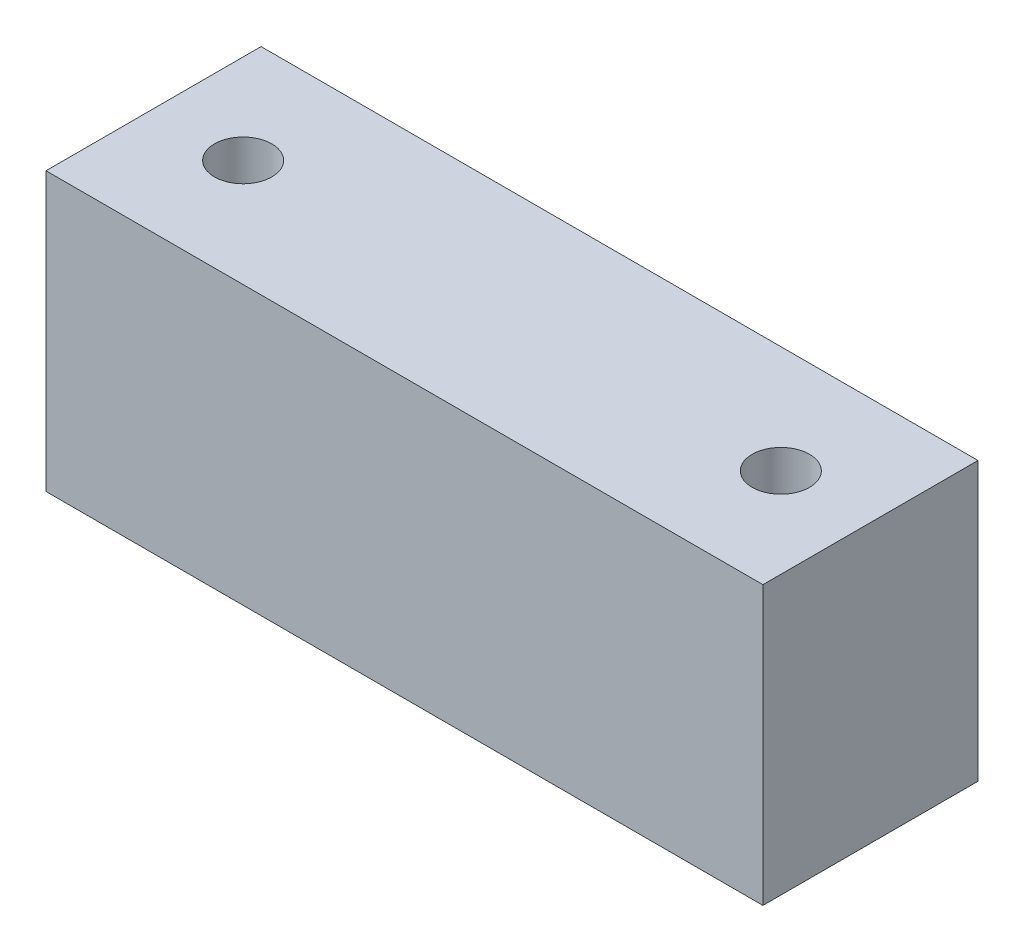
SolidWorks part; units mm, degrees
ref_plane "Front Plane" through (0, 0, 0) normal (0, 0, 1) x (1, 0, 0)
ref_plane "Top Plane" through (0, 0, 0) normal (0, 1, 0) x (1, 0, 0)
ref_plane "Right Plane" through (0, 0, 0) normal (1, 0, 0) x (0, 0, -1)
sketch "Sketch1" plane through (0, 0, 0) normal (0, 1, 0) x (1, 0, 0)
  line L1 (-20, 6) -> (20, 6)
  line L2 (-20, 6) -> (-20, -6)
  line L3 (-20, -6) -> (20, -6)
  line L4 (20, 6) -> (20, -6)
  line L5 (-20, 6) -> (20, -6) construction
  line L6 (-20, -6) -> (20, 6) construction
  point P0 (0, 0)
  dimension "D1" = 40
  dimension "D2" = 12
extrude "Boss-Extrude1" add sketch "Sketch1" along normal blind 15.5
sketch "Sketch2" plane through (0, 15.5, 0) normal (0, 1, 0) x (1, 0, 0)
  line L0 (-20, 0) -> (20, 0) construction
  line L1 (-20, 6) -> (-20, -6) construction
  line L2 (20, -6) -> (20, 6) construction
  line L3 (0, -6) -> (0, 7.5) construction
  line L4 (-20, -6) -> (20, -6) construction
  line L5 (20, 6) -> (-20, 6) construction
  circle A0 centre (15, 0) radius 1.6
  circle A1 centre (-15, 0) radius 1.6
  point P17 (0, 6)
  dimension "D1" = 3.2
  dimension "D2" = 15
extrude "Cut-Extrude2" cut sketch "Sketch2" against normal through all
sketch "Sketch3" plane through (-20, 0, 0) normal (-1, 0, 0) x (0, 0, 1)
  line L0 (-5.25, 15.5) -> (-5.25, 14.5)
  line L1 (-6, 15.5) -> (6, 15.5) construction
  line L2 (-5.25, 14.5) -> (-4.25, 14.5)
  line L3 (-4.25, 14.5) -> (-4.25, 15.5)
  line L4 (-4.25, 15.5) -> (-5.25, 15.5)
  line L5 (-3.25, 14.5) -> (-2.25, 14.5)
  line L6 (-3.25, 15.5) -> (-3.25, 14.5)
  line L7 (-2.25, 14.5) -> (-2.25, 15.5)
  line L8 (-2.25, 15.5) -> (-3.25, 15.5)
  line L9 (-1.25, 14.5) -> (-0.25, 14.5)
  line L10 (-1.25, 15.5) -> (-1.25, 14.5)
  line L11 (-0.25, 14.5) -> (-0.25, 15.5)
  line L12 (-0.25, 15.5) -> (-1.25, 15.5)
  line L13 (0.75, 14.5) -> (1.75, 14.5)
  line L14 (0.75, 15.5) -> (0.75, 14.5)
  line L15 (1.75, 14.5) -> (1.75, 15.5)
  line L16 (1.75, 15.5) -> (0.75, 15.5)
  line L17 (2.75, 14.5) -> (3.75, 14.5)
  line L18 (2.75, 15.5) -> (2.75, 14.5)
  line L19 (3.75, 14.5) -> (3.75, 15.5)
  line L20 (3.75, 15.5) -> (2.75, 15.5)
  line L21 (4.75, 14.5) -> (5.75, 14.5)
  line L22 (4.75, 15.5) -> (4.75, 14.5)
  line L23 (5.75, 14.5) -> (5.75, 15.5)
  line L24 (5.75, 15.5) -> (4.75, 15.5)
  line L25 (6.75, 14.5) -> (7.75, 14.5)
  line L26 (6.75, 15.5) -> (6.75, 14.5)
  line L27 (7.75, 14.5) -> (7.75, 15.5)
  line L28 (7.75, 15.5) -> (6.75, 15.5)
  line L29 (8.75, 14.5) -> (9.75, 14.5)
  line L30 (8.75, 15.5) -> (8.75, 14.5)
  line L31 (9.75, 14.5) -> (9.75, 15.5)
  line L32 (9.75, 15.5) -> (8.75, 15.5)
  line L33 (-6, 15.5) -> (-6, 0) construction
  dimension "D1" = 1
  dimension "D3" = 0.75
  dimension "D4" = 1
  dimension "D5" = 1
  dimension "D6" = 1
  dimension "D2" = 8
extrude "Teeth" [suppressed] cut sketch "Sketch3" against normal blind 5 and the other way blind 5 from surface
sketch "Sketch4" [suppressed] plane through (0, 5, 0) normal (0, 1, 0) x (1, 0, 0)
  line L0 (-15, 0) -> (-15, 3.4641) construction
  line L1 (-15, 3.4641) -> (-18, 1.7321)
  line L2 (-18, 1.7321) -> (-18, -1.7321)
  line L3 (-18, -1.7321) -> (-15, -3.4641)
  line L4 (-15, -3.4641) -> (-12, -1.7321)
  line L5 (-12, -1.7321) -> (-12, 1.7321)
  line L6 (-12, 1.7321) -> (-15, 3.4641)
  line L7 (0, 7.5) -> (0, -7.5) construction
  line L8 (20, 7.5) -> (-20, 7.5) construction
  line L9 (5, -7.5) -> (-5, -7.5) construction
  line L10 (15, 0) -> (15, 3.4641) construction
  line L11 (12, 1.7321) -> (15, 3.4641)
  line L12 (12, -1.7321) -> (12, 1.7321)
  line L13 (15, -3.4641) -> (12, -1.7321)
  line L14 (18, -1.7321) -> (15, -3.4641)
  line L15 (18, 1.7321) -> (18, -1.7321)
  line L16 (15, 3.4641) -> (18, 1.7321)
  line L17 (-15, 0) -> (-15, 3.4641) construction
  circle A0 centre (-15, 0) radius 3 construction
  circle A1 centre (15, 0) radius 3 construction
  dimension "D1" = 6
extrude "Cut-Extrude4" [suppressed] cut sketch "Sketch4" against normal blind 2
equation "\"X-ROD-SPACING\"=45"
equation "\"Y-ROD-SPACING\"=75"
equation "\"Z-ROD-SPACING\"=17.5"
equation "\"Y-BED-OFFSET\"=2"
equation "\"Y-BED-ROD-INSET\"=3.5"
equation "\"T-SLOT-NUT-FILLET-RADIUS\"=0.25"
equation "\"T-SLOT-SCREW-SHAFT-RADIUS\"=1.75"
equation "\"T-SLOT-SCREW-SHAFT-CUTOUT-LENGTH\"=10.5"
equation "\"T-SLOT-NUT-DEPTH\"=4.2"
equation "\"T-SLOT-NUT-WIDTH\"=3"
equation "\"T-SLOT-NUT-END-DISTANCE\"=8"
equation "\"ACRYLIC-THICKNESS\"=10"
equation "\"ACRYLIC-THICKNESS2\"=4.5"
equation "\"ACRYLIC-TAB-CUTOUT-SIZE\"=\"ACRYLIC-THICKNESS\"+\"ACRYLIC-TAB-TOLERANCE\"*2"
equation "\"ACRYLIC-TAB-WIDTH\"=\"ACRYLIC-THICKNESS\""
equation "\"ACRYLIC-M3-HOLE\"=3.2"
equation "\"SMOOTHROD-CAP-SCREW-DISTANCE\"=20"
equation "\"FRAME-WIDTH-INNER\"=370"
equation "\"NEMA17-HOLE-SPACING\"=31"
equation "\"NEMA17-CENTRAL-CUTOUT\"=22.5"
equation "\"Z-BRACKET-REACH\"=55"
equation "\"TOP-BRACKET-SPACING\"=40"
equation "\"SMOOTHROD-X-LENGTH\"=350"
equation "\"SMOOTHROD-Y-LENGTH\"=350"
equation "\"SMOOTHROD-Z-LENGTH\"=350"
equation "\"SMOOTHROD-TIGHTENING-HEADROOM\"=1"
equation "\"LEADSCREW-Z-LENGTH\"=300"
equation "\"SCREW-LENGTH-FRAME\"=\"ACRYLIC-THICKNESS\" + 10"
equation "\"SCREW-HEAD-RADIUS\"=6"
equation "\"PRINTED-X-SMOOTHROD-DIAMETER\"=8.2"
equation "\"PRINTED-X-SMOOTHROD-CUTOUT\"=10"
equation "\"PRINTED-X-BASE-HEIGHT\"=10"
equation "\"PRINTED-LM8UU-CUTOUT-SIZE\"=16"
equation "\"PRINTED-LM8UU-CUTOUT-LENGTH\"=24.5"
equation "\"PRINTED-X-IDLER-HEIGHT\"=16"
equation "\"PSU-MOUNTING-WIDTH\"=95"
equation "\"PSU-MOUNTING-HEIGHT\"=177"
equation "\"Y-BELT-TO-ROD-DISTANCE\"=20"
equation "\"D1@Sketch4\"=\"T-SLOT-NUT-WIDTH\"*2"
